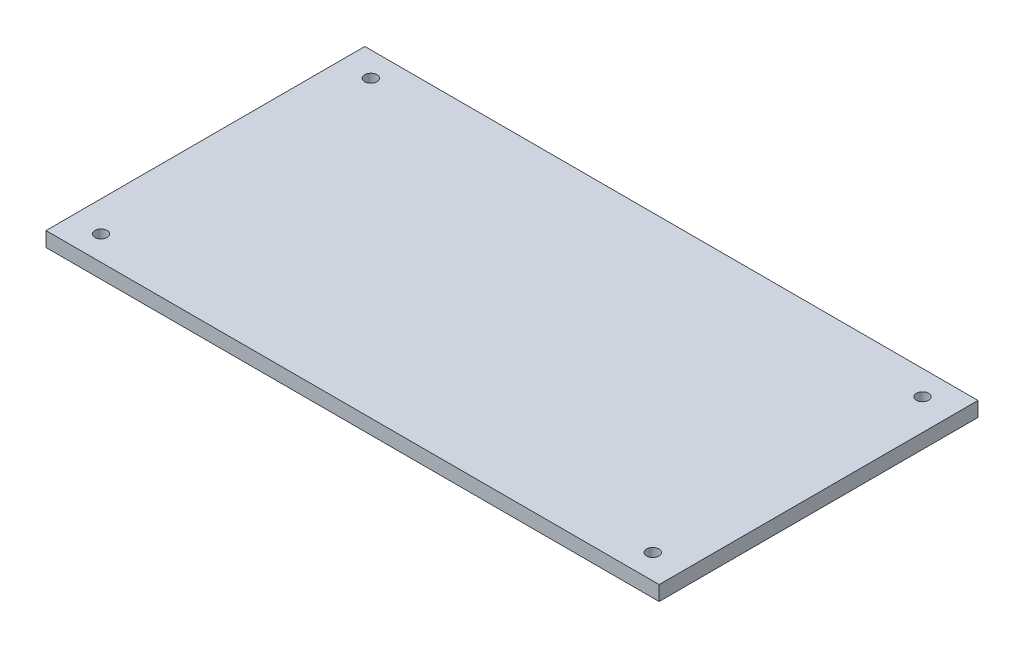
SolidWorks part; units mm, degrees
ref_plane "Front Plane" through (0, 0, 0) normal (0, 0, 1) x (1, 0, 0)
ref_plane "Top Plane" through (0, 0, 0) normal (0, 1, 0) x (1, 0, 0)
ref_plane "Right Plane" through (0, 0, 0) normal (1, 0, 0) x (0, 0, -1)
sketch "Sketch1" plane through (0, 0, 0) normal (0, 1, 0) x (1, 0, 0)
  line L0 (-125, 55) -> (125, 55) construction
  line L1 (-125, -65) -> (125, -65)
  line L2 (-125, -65) -> (-125, 65)
  line L3 (-125, 65) -> (125, 65)
  line L4 (125, -65) -> (125, 65)
  line L5 (-125, -65) -> (125, 65) construction
  line L6 (-125, 65) -> (125, -65) construction
  line L7 (-125, -55) -> (125, -55) construction
  circle A0 centre (-112.5687, 55) radius 2.5
  circle A1 centre (112.3791, 55) radius 2.5
  circle A2 centre (112.3791, -55) radius 2.5
  circle A3 centre (-112.5687, -55) radius 2.5
  point P0 (0, 0)
  dimension "D5" = 5
  dimension "D1" = 250
  dimension "D2" = 130
  dimension "D3" = 10
  dimension "D4" = 10
extrude "Boss-Extrude1" add sketch "Sketch1" along normal blind 6 contours L3 L4 L1 L2
extrude "Cut-Extrude1" cut sketch "Sketch1<4>" along normal blind 6 contours A2 | A1 | A0 | A3
sketch "Sketch1<4>" plane through (0, 0, 0) normal (0, 1, 0) x (1, 0, 0) same geometry as "Sketch1"
